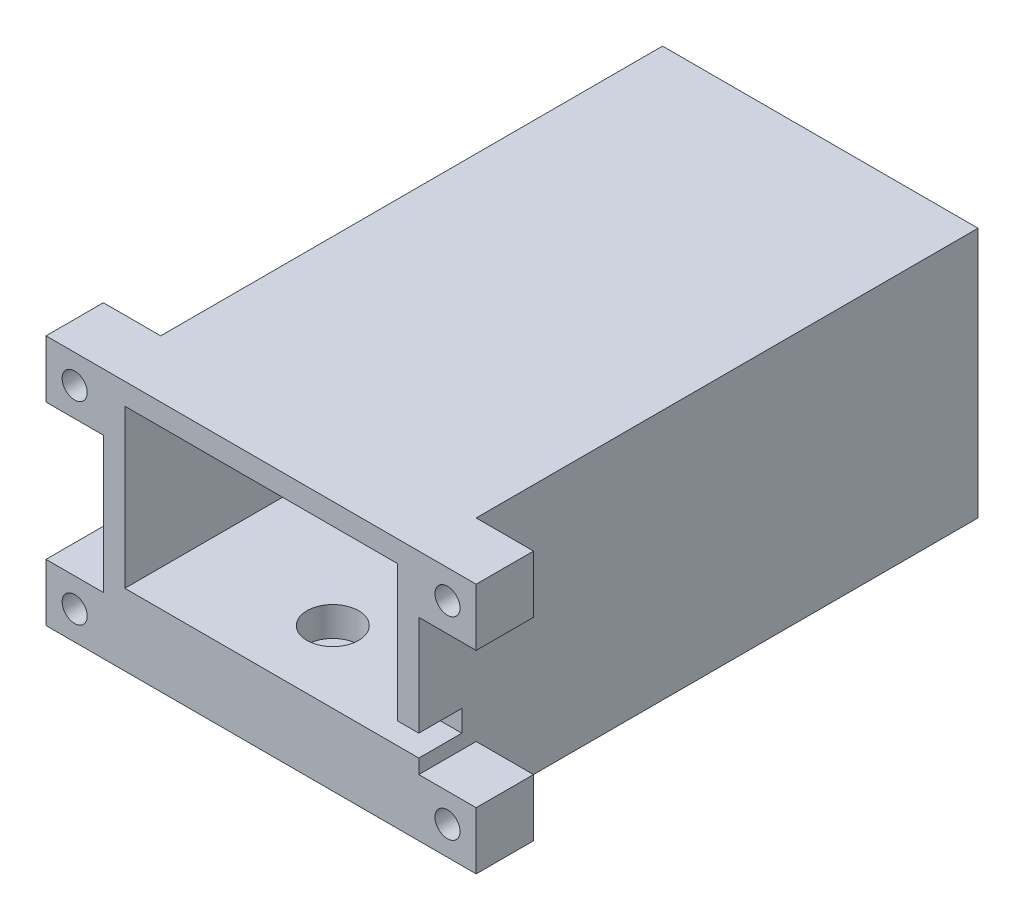
SolidWorks part; units mm, degrees
ref_plane "前基準面" through (0, 0, 0) normal (0, 0, 1) x (1, 0, 0)
ref_plane "上基準面" through (0, 0, 0) normal (0, 1, 0) x (1, 0, 0)
ref_plane "右基準面" through (0, 0, 0) normal (1, 0, 0) x (0, 0, -1)
sketch "草圖1" plane through (0, 0, 0) normal (0, 1, 0) x (1, 0, 0)
  line L1 (-22, 39) -> (22, 39)
  line L2 (-22, 39) -> (-22, -39)
  line L3 (-22, -39) -> (22, -39)
  line L4 (22, 39) -> (22, -39)
  line L5 (-22, 39) -> (22, -39) construction
  line L6 (-22, -39) -> (22, 39) construction
  point P0 (0, 0)
  dimension "D1" = 78
  dimension "D2" = 44
extrude "填料-伸長1" add sketch "草圖1" along normal blind 35
shell "薄殼1" thickness 3 removed face at (0, 17.5, 39)
sketch "草圖3" plane through (0, 10, 0) normal (0, 1, 0) x (1, 0, 0)
  line L0 (-22, -39) -> (22, -39) construction
  circle A0 centre (0, 25) radius 3.6
  circle A1 centre (0, -29) radius 3.6
  point P6 (-0.1288, -21.7602)
  dimension "D1" = 7.2
  dimension "D2" = 54
  dimension "D3" = 10
extrude "除料-伸長1" cut sketch "草圖3" against normal blind 4.1
sketch "草圖4" plane through (0, 10, 0) normal (0, 1, 0) x (1, 0, 0)
  circle A0 centre (0, 25) radius 2.25
  circle A1 centre (0, -29) radius 2.25
  dimension "D1" = 4.5
extrude "除料-伸長2" cut sketch "草圖4" against normal up to next
sketch "草圖5" plane through (0, 0, 39) normal (0, 0, 1) x (1, 0, 0)
  line L0 (22, 35) -> (22, 0) construction
  line L1 (19, 10) -> (22, 10)
  line L2 (19, 10) -> (19, 13)
  line L3 (19, 13) -> (22, 13)
  line L4 (22, 10) -> (22, 13)
  dimension "D1" = 3
extrude "除料-伸長3" cut sketch "草圖5" against normal blind 6
sketch "草圖6" plane through (0, 0, 39) normal (0, 0, 1) x (1, 0, 0)
  line L0 (0, 0) -> (0, 15.8602) construction
  line L1 (-30, 27) -> (-22, 27)
  line L2 (-30, 27) -> (-30, 35)
  line L3 (-30, 35) -> (-22, 35)
  line L4 (-22, 27) -> (-22, 35)
  line L5 (-30, 27) -> (-22, 35) construction
  line L6 (-30, 35) -> (-22, 27) construction
  line L7 (-30, 8) -> (-22, 8)
  line L8 (-30, 8) -> (-30, 0)
  line L9 (-30, 0) -> (-22, 0)
  line L10 (-22, 8) -> (-22, 0)
  line L11 (-30, 8) -> (-22, 0) construction
  line L12 (-30, 0) -> (-22, 8) construction
  line L13 (30, 0) -> (22, 8) construction
  line L14 (30, 8) -> (22, 0) construction
  line L15 (30, 35) -> (22, 27) construction
  line L16 (30, 27) -> (22, 35) construction
  line L17 (22, 8) -> (22, 0)
  line L18 (30, 0) -> (22, 0)
  line L19 (30, 8) -> (30, 0)
  line L20 (30, 8) -> (22, 8)
  line L21 (22, 27) -> (22, 35)
  line L22 (30, 35) -> (22, 35)
  line L23 (30, 27) -> (30, 35)
  line L24 (30, 27) -> (22, 27)
  circle A0 centre (-26, 31) radius 1.75
  circle A1 centre (-26, 4) radius 1.75
  circle A2 centre (26, 31) radius 1.75
  circle A3 centre (26, 4) radius 1.75
  point P0 (-26, 31)
  point P6 (-26, 4)
  point P23 (26, 4)
  point P24 (26, 31)
  dimension "D2" = 3.5
  dimension "D1" = 8
extrude "填料-伸長2" add sketch "草圖6" against normal blind 8
sketch "草圖7" plane through (0, 0, 31) normal (0, 0, -1) x (-1, 0, 0)
  line L0 (0, 0) -> (0, 11.4673) construction
  line L1 (27.5877, 6.75) -> (29.1754, 4)
  line L2 (-22.8246, 31) -> (-24.4123, 33.75)
  line L3 (-24.4123, 33.75) -> (-27.5877, 33.75)
  line L4 (-27.5877, 33.75) -> (-29.1754, 31)
  line L5 (-29.1754, 31) -> (-27.5877, 28.25)
  line L6 (-27.5877, 28.25) -> (-24.4123, 28.25)
  line L7 (-24.4123, 28.25) -> (-22.8246, 31)
  line L8 (-29.1754, 4) -> (-27.5877, 1.25)
  line L9 (-27.5877, 1.25) -> (-24.4123, 1.25)
  line L10 (-24.4123, 1.25) -> (-22.8246, 4)
  line L11 (-22.8246, 4) -> (-24.4123, 6.75)
  line L12 (-24.4123, 6.75) -> (-27.5877, 6.75)
  line L13 (-27.5877, 6.75) -> (-29.1754, 4)
  line L14 (24.4123, 6.75) -> (27.5877, 6.75)
  line L15 (22.8246, 4) -> (24.4123, 6.75)
  line L16 (24.4123, 1.25) -> (22.8246, 4)
  line L17 (27.5877, 1.25) -> (24.4123, 1.25)
  line L18 (29.1754, 4) -> (27.5877, 1.25)
  line L19 (24.4123, 28.25) -> (22.8246, 31)
  line L20 (27.5877, 28.25) -> (24.4123, 28.25)
  line L21 (29.1754, 31) -> (27.5877, 28.25)
  line L22 (27.5877, 33.75) -> (29.1754, 31)
  line L23 (24.4123, 33.75) -> (27.5877, 33.75)
  line L24 (22.8246, 31) -> (24.4123, 33.75)
  circle A0 centre (-26, 31) radius 2.75 construction
  circle A1 centre (-26, 4) radius 2.75 construction
  circle A2 centre (26, 4) radius 2.75 construction
  circle A3 centre (26, 31) radius 2.75 construction
  dimension "D1" = 5.5
extrude "除料-伸長4" cut sketch "草圖7" against normal blind 2.6
